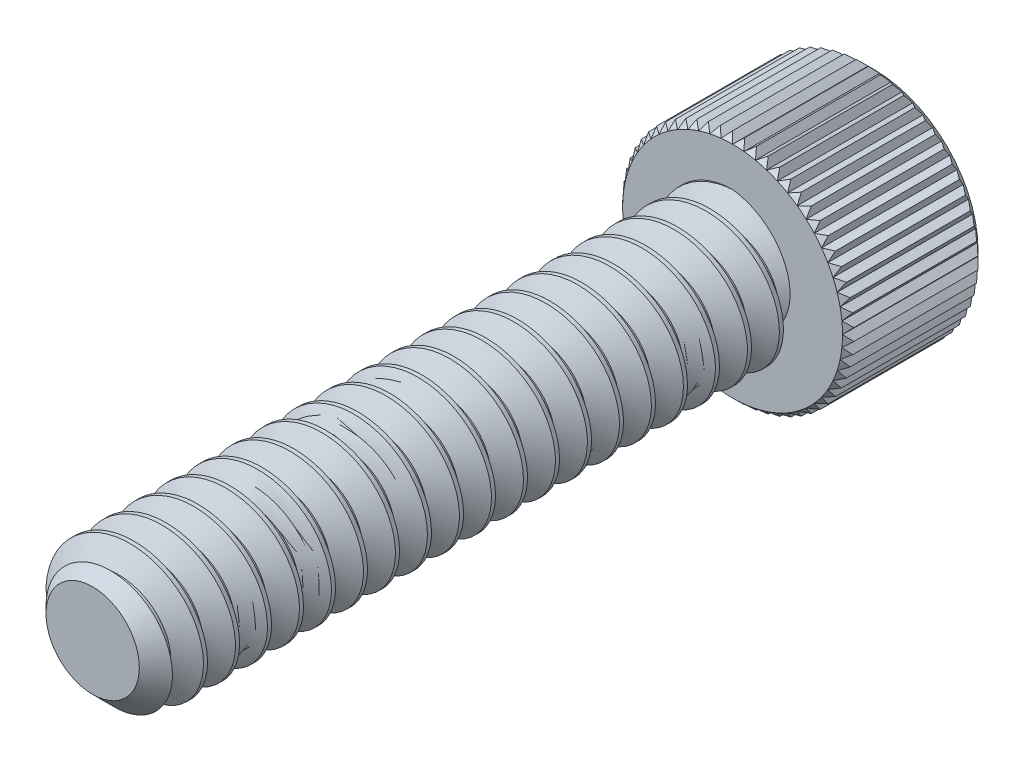
SolidWorks part; units mm, degrees
note: '?' marks a value the reader was unsure of.
ref_plane "Front Plane" through (0, 0, 0) normal (0, 0, 1) x (1, 0, 0)
ref_plane "Top Plane" through (0, 0, 0) normal (0, 1, 0) x (1, 0, 0)
ref_plane "Right Plane" through (0, 0, 0) normal (1, 0, 0) x (0, 0, -1)
sketch "Sketch0" plane through (0, 0, 0) normal (1, 0, 0) x (0, 0, -1)
  line L0 (0, 0) -> (15.875, 0) construction
  point P2 (19.3802, 0)
  point P4 (0, 0)
  dimension "D1" = 15.875
  dimension "D2" = 3.5052
  dimension "Min Thread" = 0
sketch "Sketch1" plane through (0, 0, 0) normal (0, 0, 1) x (1, 0, 0)
  circle A0 centre (0, 0) radius 1.7526
  dimension "OD" = 3.5052
extrude "Extrude1" add sketch "Sketch1" against normal blind 15.875
sketch "Sketch2" plane through (0, 0, 0) normal (0, 0, 1) x (1, 0, 0)
  circle A0 centre (0, 0) radius 1.7526 construction
  circle A1 centre (0, 0) radius 1.7526
curve "Helix/Spiral1" pitch 0.7937 height 16.6687 turns 21 parameters "pitch"=0.7937
chamfer "Chamfer3" distance 0.5953 angle 45 1 edges at (1.7526, 0, 0)
sketch "Sketch3" plane through (0, 0, 0) normal (1, 0, 0) x (0, 0, -1)
  line L0 (-0.6945, 1.7526) -> (-0.3969, 1.237)
  line L1 (-0.3969, 1.237) -> (-0.2977, 1.237)
  line L2 (-0.2977, 1.237) -> (0, 1.7526)
  line L3 (-0.6945, 1.7526) -> (0, 1.7526)
  line L4 (-0.3473, 1.7526) -> (-0.3473, 1.237) construction
  line L5 (-0.5457, 1.4948) -> (-0.1488, 1.4948) construction
  line L6 (0, 1.7526) -> (0, -1.7526) construction
  dimension "D1" = 0.0992
  dimension "D2" = 0.3969
  dimension "D3" = 60
sweep "Cut-Sweep1" cut profiles "Sketch3" path "Helix/Spiral1"
sketch "Sketch5" plane through (0, 0, 0) normal (1, 0, 0) x (0, 0, -1)
  line L0 (15.875, -1.2539) -> (15.875, 1.2505) construction
  line L1 (15.875, 1.7526) -> (0, 1.7526)
  line L2 (15.875, 1.7526) -> (15.875, 0)
  line L3 (15.875, 0) -> (-0.6379, 0)
  line L4 (0, 0) -> (15.875, 0) construction
  line L5 (0, 1.7526) -> (-0.6379, 0)
  line L6 (0, 0) -> (18.415, 0) construction
  dimension "D1" = 70
  dimension "D3" = 2.54
revolve "partially thread" [suppressed] add sketch "Sketch5" angle 360 about L6
sketch "Sketch6" plane through (0, 0, -15.875) normal (0, 0, -1) x (-1, 0, 0)
  circle A0 centre (0, 0) radius 2.8702
  dimension "head dia" = 5.7404
extrude "Extrude2" add sketch "Sketch6" along normal blind 3.5052
sketch "Sketch7" plane through (0, 0, -19.3802) normal (0, 0, -1) x (-1, 0, 0)
  line L1 (0, 1.604) -> (-1.3891, 0.802)
  line L2 (-1.3891, 0.802) -> (-1.3891, -0.802)
  line L3 (-1.3891, -0.802) -> (0, -1.604)
  line L4 (0, -1.604) -> (1.3891, -0.802)
  line L5 (1.3891, -0.802) -> (1.3891, 0.802)
  line L6 (1.3891, 0.802) -> (0, 1.604)
  circle A0 centre (0, 0) radius 1.3891 construction
  dimension "hex dia" = 2.7781
extrude "Cut-Extrude1" cut sketch "Sketch7" against normal blind 2.0836
sketch "Sketch8" plane through (0, 0, -19.3802) normal (0, 0, -1) x (-1, 0, 0)
  circle A0 centre (0, 0) radius 1.604
extrude "Cut-Extrude2" cut sketch "Sketch8" against normal through all draft 45
chamfer "Chamfer1" distance 0.287 angle 45 1 edges at (-2.8702, 0, -19.3802)
chamfer "Chamfer2" distance 0.1435 angle 45 1 edges at (-2.8702, 0, -15.875)
sketch "Sketch9" plane through (0, 0, 0) normal (1, 0, 0) x (0, 0, -1)
  line L0 (0, 1.7526) -> (0, -1.7526) construction
  line L1 (1.9844, 1.7526) -> (1.9844, -1.7526) construction
  line L2 (19.3802, 2.8702) -> (19.3802, -2.8702) construction
  line L3 (15.875, 2.8702) -> (15.875, -2.8702) construction
  line L4 (15.875, 2.7267) -> (15.875, -2.7267) construction
  line L5 (19.3802, -2.5832) -> (19.3802, 2.5832) construction
  line L6 (15.875, -2.8702) -> (15.875, 2.8702) construction
  line L7 (0, 1.1573) -> (0, -1.1573) construction
  line L8 (-0.6945, 1.7526) -> (0, 1.7526) construction
  line L9 (1.9844, 0) -> (0, 0) construction
  dimension "D1" = 1.9844
sketch "Sketch10" plane through (0, 0, -15.875) normal (0, 0, 1) x (1, 0, 0)
  line L0 (-0.3089, 3.0137) -> (0, 2.7267)
  line L1 (0, 2.7267) -> (0.3089, 3.0137)
  line L2 (0, 2.7267) -> (0, 3.0137) construction
  line L3 (-0.3089, 3.0137) -> (0.3089, 3.0137)
  line L4 (0, -2.8599) -> (0, 2.8599) construction
  line L5 (0, 0) -> (0.1502, 2.8663) construction
  line L6 (-0.1502, 2.8663) -> (0, 0) construction
  circle A2 centre (0, 0) radius 2.8702 construction
  circle A5 centre (0, 0) radius 2.7267 construction
  dimension "D1" = 6
  dimension "D2" = 0.287
extrude "Cut-Extrude3" cut sketch "Sketch10" against normal through all
pattern_circular "CirPattern1" count 60 over 360 about axis through (0, 0, 0) along (0, 0, 1) of "Cut-Extrude3"
ref_plane "Contact Plane 1" through (0, 0, -15.875) normal (0, 0, 1) x (1, 0, 0)
ref_axis "Center Axis 1" through (0, 0, 0.8878) along (0, 0, -1)?
equation "\"D3@Helix/Spiral1\" = \"screw length@Extrude1\"+\"pitch@Helix/Spiral1\""
equation "\"D1@Sketch3\" = \"pitch@Helix/Spiral1\"*.125"
equation "\"D2@Sketch3\" = \"pitch@Helix/Spiral1\"*.5"
equation "\"D1@Cut-Extrude1\" = \"hex dia@Sketch7\"*.75"
equation "\"D1@Chamfer1\" = \"head dia@Sketch6\"*.05"
equation "\"D1@Sketch9\" = \"pitch@Helix/Spiral1\"*2.50"
equation "\"D1@Chamfer2\" = \"D1@Chamfer1\"/2"
equation "\"D1@Chamfer3\" = \"pitch@Helix/Spiral1\"*.750"
equation "\"D1@Sketch0\" = \"screw length@Extrude1\""
equation "\"D2@Sketch0\" = \"head depth@Extrude2\""
equation "\"D2@Sketch10\"=\"D1@Chamfer1\""
equation "\"D1@CirPattern1\"=\"D3@CirPattern1\"/\"D1@Sketch10\""
